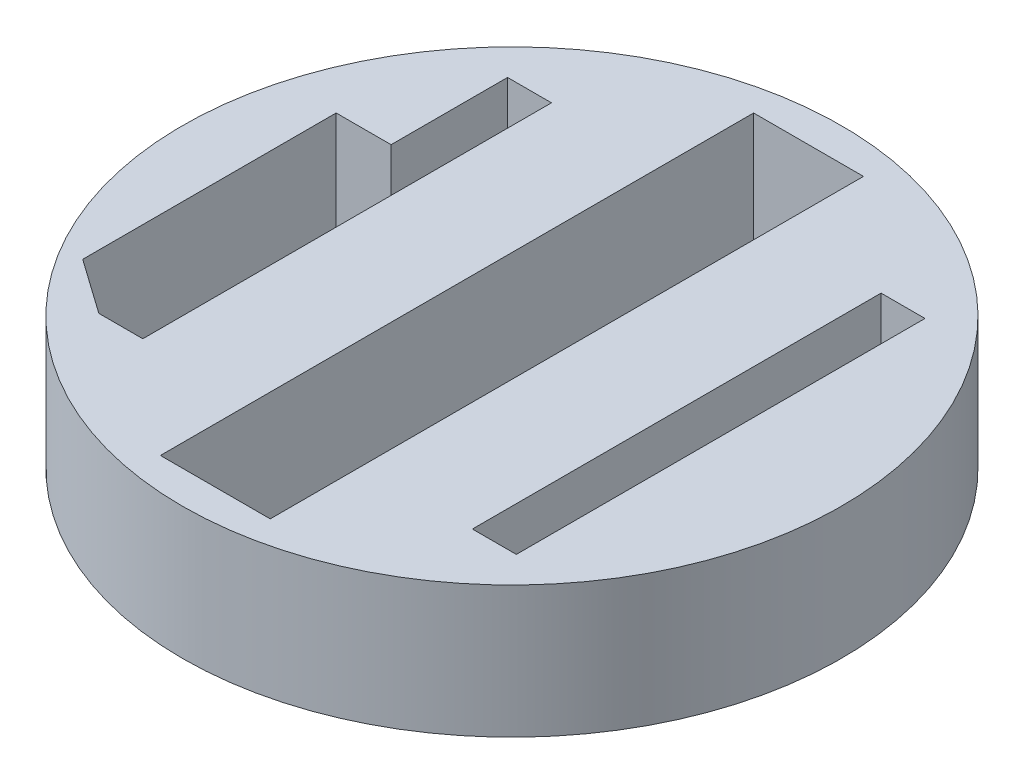
SolidWorks part; units mm, degrees
ref_plane "Спереди" through (0, 0, 0) normal (0, 0, 1) x (1, 0, 0)
ref_plane "Сверху" through (0, 0, 0) normal (0, 1, 0) x (1, 0, 0)
ref_plane "Справа" through (0, 0, 0) normal (1, 0, 0) x (0, 0, -1)
sketch "Эскиз3" plane through (0, 0, 0) normal (0, 1, 0) x (1, 0, 0)
  circle A0 centre (0, 0) radius 15
extrude "Бобышка-Вытянуть2" add sketch "Эскиз3" along normal blind 6
sketch "Эскиз8" plane through (0, 6, 0) normal (0, 1, 0) x (1, 0, 0)
  line L0 (0, 21.5769) -> (0, -20.9711) construction
  line L5 (-12, -4) -> (-12, -7.5369)
  line L6 (-12, -7.5369) -> (-9.5, -9.3)
  line L7 (7.5, 9.3) -> (9.5, 9.3)
  line L8 (7.5, 9.3) -> (7.5, -9.3)
  line L9 (7.5, -9.3) -> (9.5, -9.3)
  line L10 (9.5, 9.3) -> (9.5, -9.3)
  line L11 (-23.6577, 0) -> (29.9171, 0) construction
  line L12 (-9.5, 9.3) -> (-9.5, 4)
  line L13 (-9.5, 9.3) -> (-7.5, 9.3)
  line L15 (-9.5, -9.3) -> (-7.5, -9.3)
  line L16 (-7.5, 9.3) -> (-7.5, -9.3)
  line L17 (-12, 4) -> (-9.5, 4)
  line L18 (-12, 4) -> (-12, -4)
  circle A0 centre (0, 0) radius 15 construction
  point P2 (0, 0)
  point P4 (-12, -7.5369)
  point P15 (7.5, 0)
  point P24 (-7.5, 0)
  dimension "D2" = 2
  dimension "D3" = 18.6
  dimension "D4" = 2
  dimension "D5" = 12
  dimension "D7" = 2
  dimension "D8" = 18.6
  dimension "D9" = 8
  dimension "D10" = 5.3
  dimension "D11" = 7.5
extrude "Вырез-Вытянуть1" cut sketch "Эскиз8" against normal through all
sketch "Эскиз9" plane through (0, 6, 0) normal (0, 1, 0) x (1, 0, 0)
  line L1 (-2.5, -13.5) -> (2.5, -13.5)
  line L2 (-2.5, -13.5) -> (-2.5, 13.5)
  line L3 (-2.5, 13.5) -> (2.5, 13.5)
  line L4 (2.5, -13.5) -> (2.5, 13.5)
  line L5 (-2.5, -13.5) -> (2.5, 13.5) construction
  line L6 (-2.5, 13.5) -> (2.5, -13.5) construction
  point P0 (0, 0)
  dimension "D1" = 27
  dimension "D2" = 5
extrude "Вырез-Вытянуть2" cut sketch "Эскиз9" against normal through all
